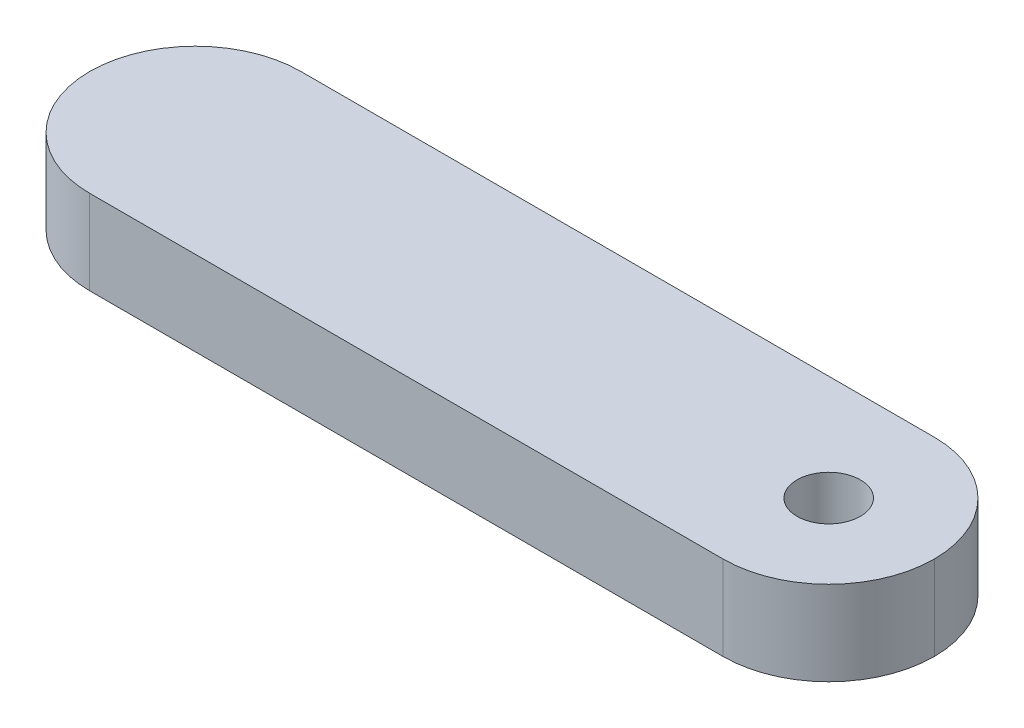
SolidWorks part; units mm, degrees
ref_plane "Plano frontal" through (0, 0, 0) normal (0, 0, 1) x (1, 0, 0)
ref_plane "Plano superior" through (0, 0, 0) normal (0, 1, 0) x (1, 0, 0)
ref_plane "Plano direito" through (0, 0, 0) normal (1, 0, 0) x (0, 0, -1)
sketch "Esboço2" plane through (0, 0, 0) normal (0, 1, 0) x (1, 0, 0)
  line L1 (-200, -50) -> (200, -50)
  line L2 (-200, -50) -> (-200, 50)
  line L3 (-200, 50) -> (200, 50)
  line L4 (200, -50) -> (200, 50)
  line L5 (-200, -50) -> (200, 50) construction
  line L6 (-200, 50) -> (200, -50) construction
  point P0 (0, 0)
  dimension "D1" = 100
  dimension "D2" = 400
extrude "Ressalto-extrusão1" add sketch "Esboço2" along normal blind 40
fillet "Filete1" radius 50 4 edges at (-200, 20, -50) (-200, 20, 50) (200, 20, -50) (200, 20, 50)
sketch "Esboço3" plane through (0, 40, 0) normal (0, 1, 0) x (1, 0, 0)
  circle A1 centre (150, 0) radius 15
  dimension "D2" = 30
sketch "Esboço5" plane through (0, 0, 0) normal (0, -1, 0) x (1, 0, 0)
  circle A0 centre (-150, 0) radius 15
  point P3 (0, 0)
  dimension "D1" = 30
extrude "Corte-extrusão1" cut sketch "Esboço5" against normal blind 25
extrude "Corte-extrusão2" cut sketch "Esboço3" against normal blind 25 contours A1
